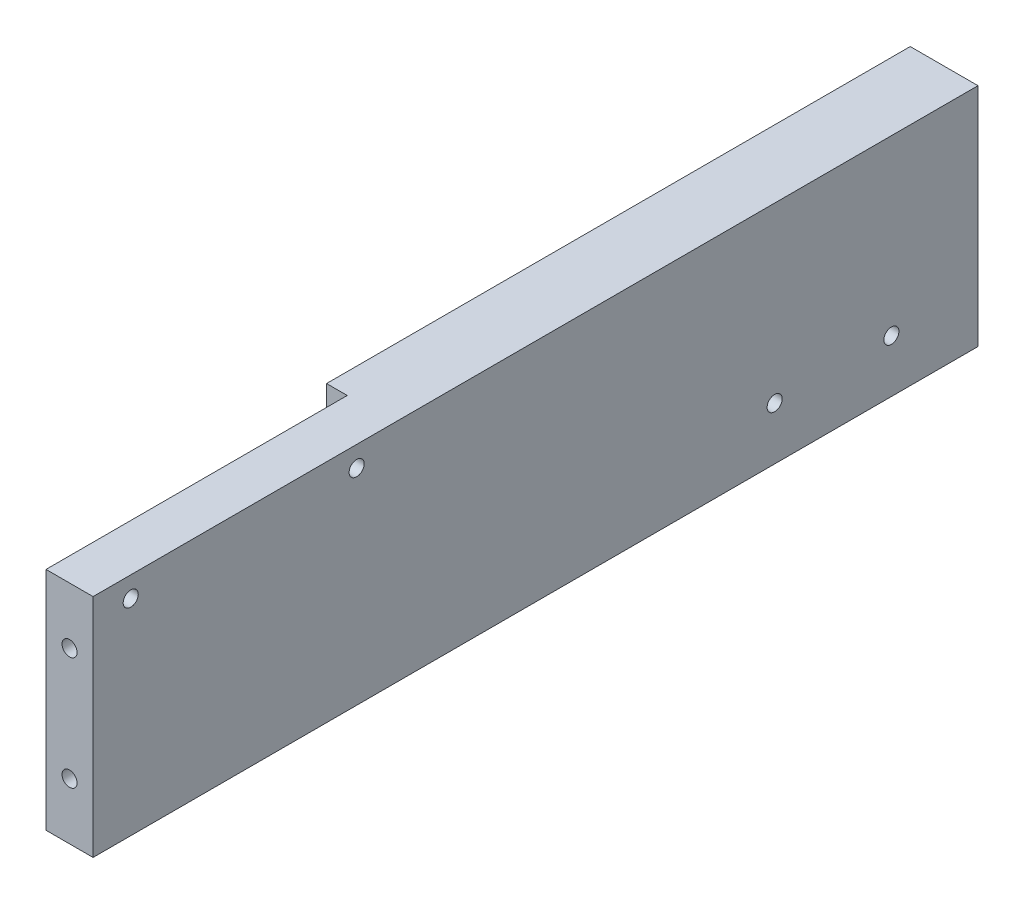
SolidWorks part; units mm, degrees
material "Pin"
ref_plane "Plan de face" through (0, 0, 0) normal (0, 0, 1) x (1, 0, 0)
ref_plane "Plan de dessus" through (0, 0, 0) normal (0, 1, 0) x (1, 0, 0)
ref_plane "Plan de droite" through (0, 0, 0) normal (1, 0, 0) x (0, 0, -1)
sketch "Esquisse1" plane through (0, 0, 0) normal (1, 0, 0) x (0, 0, -1)
  line L0 (-54.8268, 2.55) -> (-54.8268, -52) construction
  line L1 (-64.8268, 8) -> (170.1732, 8)
  line L2 (-64.8268, 8) -> (-64.8268, -52)
  line L3 (-64.8268, -52) -> (170.1732, -52)
  line L4 (170.1732, 8) -> (170.1732, -52)
  line L5 (5.1732, 2.55) -> (5.1732, -52) construction
  line L6 (147.1732, -38) -> (161.1732, -38) construction
  line L7 (147.1732, -38) -> (116.1732, -38) construction
  line L8 (116.1732, -38) -> (102.1732, -38) construction
  line L9 (-54.8268, 2.55) -> (-54.8268, 8) construction
  line L10 (-64.8268, 2.55) -> (-54.8268, 2.55) construction
  line L11 (-54.8268, 2.55) -> (5.1732, 2.55) construction
  line L12 (5.1732, 2.55) -> (170.1732, 2.55) construction
  line L13 (5.1732, 8) -> (5.1732, 2.55) construction
  line L14 (147.1732, -38) -> (147.1732, -52) construction
  line L15 (15.1732, 8) -> (15.1732, -52)
  line L16 (161.1732, -38) -> (170.1732, -38) construction
  line L17 (102.1732, -38) -> (102.1732, 8) construction
  circle A0 centre (-54.8268, 2.55) radius 2
  circle A1 centre (5.1732, 2.55) radius 2
  circle A2 centre (147.1732, -38) radius 2
  circle A3 centre (116.1732, -38) radius 2
  dimension "D4" = 4
  dimension "D9" = 4
  dimension "D1" = 60
  dimension "D2" = 235
  dimension "D3" = 54.55
  dimension "D5" = 60
  dimension "D6" = 10
  dimension "D7" = 9
  dimension "D8" = 14
  dimension "D10" = 80
  dimension "D11" = 68
extrude "Boss.-Extru.1" add sketch "Esquisse1" against normal blind 18 contours L1 L15 L3 L4 A3 A2 region at (0, -21.9566, -92.5675)
extrude "Boss.-Extru.2" add sketch "Esquisse1<5>" against normal blind 12.5 contours L15 L1 L2 L3 A1 A0 region at (0, -22.1292, 24.8268)
sketch "Esquisse1<5>" plane through (0, 0, 0) normal (1, 0, 0) x (0, 0, -1) same geometry as "Esquisse1"
sketch "Esquisse6" plane through (0, 0, 64.8268) normal (0, 0, 1) x (1, 0, 0)
  line L0 (-6.25, 8) -> (-6.25, -7) construction
  line L1 (-12.5, 8) -> (0, 8) construction
  line L2 (-6.25, -7) -> (-6.25, -37) construction
  line L3 (-6.25, -37) -> (-6.25, -52) construction
  line L4 (-12.5, -52) -> (0, -52) construction
  circle A0 centre (-6.25, -7) radius 2
  circle A1 centre (-6.25, -37) radius 2
  dimension "D1" = 4
  dimension "D2" = 15
extrude "Enlèv. mat.-Extru.2" cut sketch "Esquisse6" against normal blind 10
